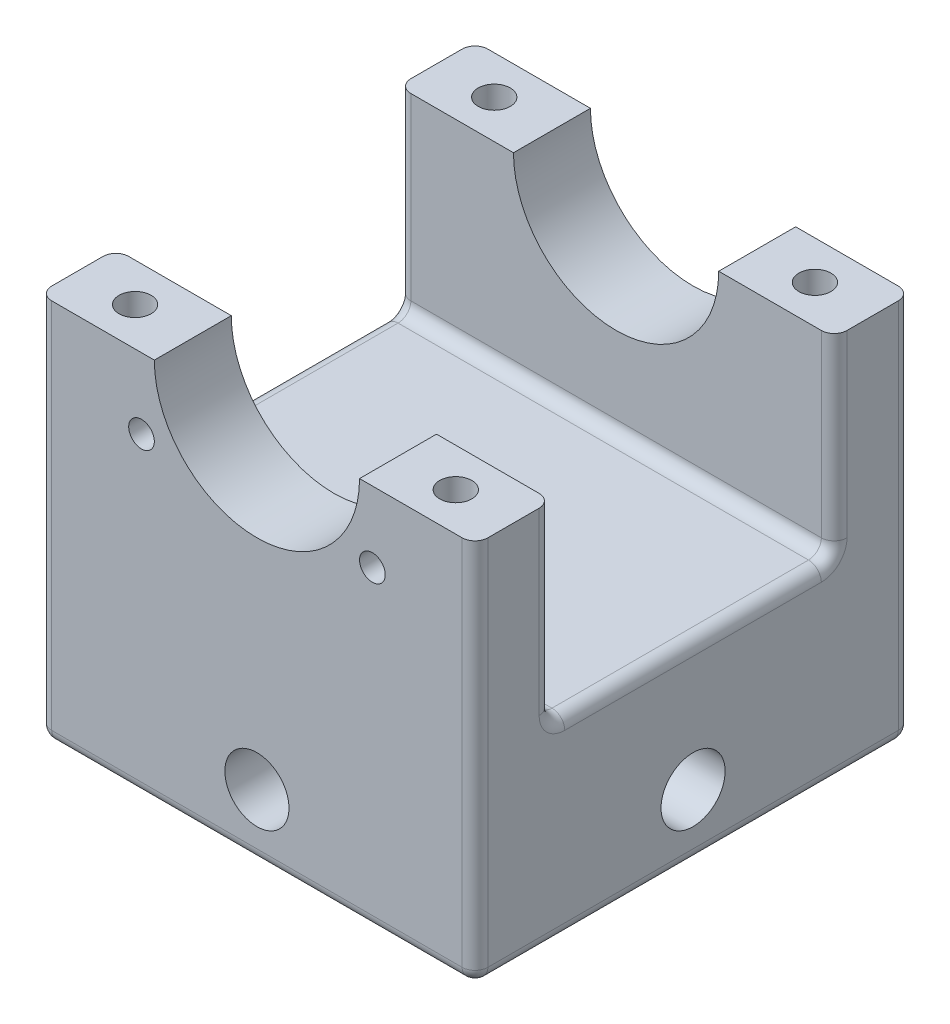
SolidWorks part; units mm, degrees
ref_plane "Front Plane" through (0, 0, 0) normal (0, 0, 1) x (1, 0, 0)
ref_plane "Top Plane" through (0, 0, 0) normal (0, 1, 0) x (1, 0, 0)
ref_plane "Right Plane" through (0, 0, 0) normal (1, 0, 0) x (0, 0, -1)
sketch "Sketch1" plane through (0, 0, 0) normal (0, 1, 0) x (1, 0, 0)
  line L1 (-17, 17) -> (17, 17)
  line L2 (-17, 17) -> (-17, -17)
  line L3 (-17, -17) -> (17, -17)
  line L4 (17, 17) -> (17, -17)
  line L5 (-17, 17) -> (17, -17) construction
  line L6 (-17, -17) -> (17, 17) construction
  point P0 (0, 0)
  dimension "D1" = 34
  dimension "D2" = 34
extrude "Boss-Extrude1" add sketch "Sketch1" along normal blind 15
sketch "Sketch2" plane through (0, 0, 0) normal (0, -1, 0) x (1, 0, 0)
  line L1 (-10.1, -10.1) -> (10.1, -10.1)
  line L2 (-10.1, -10.1) -> (-10.1, 10.1)
  line L3 (-10.1, 10.1) -> (10.1, 10.1)
  line L4 (10.1, -10.1) -> (10.1, 10.1)
  line L5 (-10.1, -10.1) -> (10.1, 10.1) construction
  line L6 (-10.1, 10.1) -> (10.1, -10.1) construction
  point P0 (0, 0)
  dimension "D1" = 20.2
  dimension "D2" = 20.2
extrude "Cut-Extrude1" cut sketch "Sketch2" against normal blind 10
sketch "Sketch4" plane through (0, 0, 17) normal (0, 0, 1) x (1, 0, 0)
  line L0 (-17, 30) -> (-17, 15)
  line L1 (-17, 15) -> (17, 15)
  line L2 (17, 15) -> (17, 30)
  line L3 (17, 30) -> (-17, 30)
  dimension "D1" = 15
extrude "Boss-Extrude2" add sketch "Sketch4" against normal blind 6
sketch "Sketch7" plane through (0, 0, 17) normal (0, 0, 1) x (1, 0, 0)
  line L0 (17, 30) -> (-17, 30) construction
  circle A0 centre (0, 30) radius 8
  dimension "D1" = 16
extrude "Cut-Extrude4" cut sketch "Sketch7" against normal through all
sketch "Sketch17" plane through (0, 30, 0) normal (0, 1, 0) x (1, 0, 0)
  line L0 (-17, -14) -> (-8, -14) construction
  line L1 (-17, -11) -> (-17, -17) construction
  line L2 (-8, -11) -> (-8, -17) construction
  line L3 (8, -14) -> (17, -14) construction
  line L4 (8, -17) -> (8, -11) construction
  line L5 (17, -11) -> (17, -17) construction
  circle A0 centre (-12.5, -14) radius 1.25
  circle A1 centre (12.5, -14) radius 1.25
  dimension "D1" = 2.5
  dimension "D2" = 2.5
extrude "Cut-Extrude10" cut sketch "Sketch17" against normal blind 10
mirror "Mirror1" about plane through (0, 0, 0) normal (0, 0, 1) of "Cut-Extrude10", "Boss-Extrude2", "Cut-Extrude4"
sketch "Sketch15" plane through (0, 0, -17) normal (0, 0, -1) x (-1, 0, 0)
  line L0 (17, 0) -> (-17, 0) construction
  circle A0 centre (0, 5) radius 2.5
  dimension "D1" = 5
  dimension "D2" = 5
extrude "Cut-Extrude8" cut sketch "Sketch15" against normal through all
sketch "Sketch16" plane through (17, 0, 0) normal (1, 0, 0) x (0, 0, -1)
  circle A0 centre (0, 5) radius 2.5
  dimension "D1" = 5
  dimension "D2" = 5
extrude "Cut-Extrude9" cut sketch "Sketch16" against normal through all
fillet "Fillet2" radius 1 16 edges at (17, 15, -17) (-17, 15, 17) (17, 15, 17) (-17, 0, 0) (0, 0, -17) (17, 0, 0) (0, 0, 17) (-17, 15, -17) (17, 22.5, -11) (0, 15, -11) (-17, 22.5, -11)
sketch "Sketch19" plane through (0, 0, 17) normal (0, 0, 1) x (1, 0, 0)
  circle A0 centre (-9, 24.5) radius 1
  arc A1 (-8, 30) -> (8, 30) centre (0, 30) ccw construction
  dimension "D1" = 2
  dimension "D2" = 9
  dimension "D3" = 5.5
extrude "Cut-Extrude12" cut sketch "Sketch19" against normal blind 3
mirror "Mirror2" about plane through (0, 0, 0) normal (1, 0, 0) of "Cut-Extrude12"
